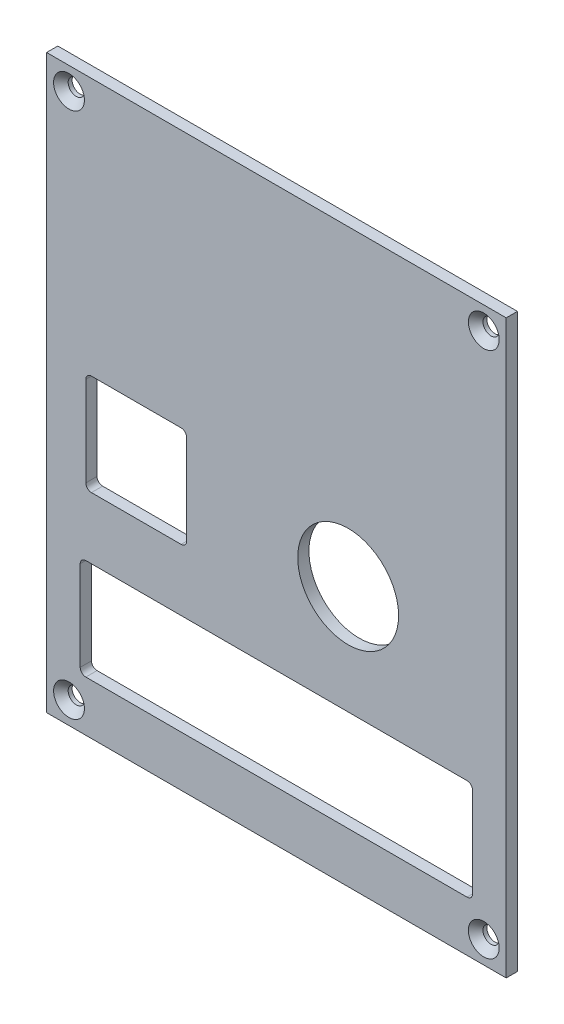
SolidWorks part; units mm, degrees
ref_plane "Front Plane" through (0, 0, 0) normal (0, 0, 1) x (1, 0, 0)
ref_plane "Top Plane" through (0, 0, 0) normal (0, 1, 0) x (1, 0, 0)
ref_plane "Right Plane" through (0, 0, 0) normal (1, 0, 0) x (0, 0, -1)
sketch "Sketch1" plane through (0, 0, 0) normal (0, 0, 1) x (1, 0, 0)
  line L1 (-49.4982, 55.7269) -> (32.5018, 55.7269)
  line L2 (-49.4982, 55.7269) -> (-49.4982, -46.2731)
  line L3 (-49.4982, -46.2731) -> (32.5018, -46.2731)
  line L4 (32.5018, 55.7269) -> (32.5018, -46.2731)
  dimension "D1" = 82
  dimension "D2" = 102
extrude "Boss-Extrude1" add sketch "Sketch1" along normal blind 2
sketch "Sketch2" plane through (0, 0, 2) normal (0, 0, 1) x (1, 0, 0)
  line L3 (-42.4982, -19.2731) -> (25.5018, -19.2731)
  line L4 (-43.4982, -20.2731) -> (-43.4982, -36.2731)
  line L5 (-42.4982, -37.2731) -> (25.5018, -37.2731)
  line L6 (26.5018, -20.2731) -> (26.5018, -36.2731)
  line L7 (-49.4982, 55.7269) -> (-49.4982, -46.2731) construction
  line L8 (-49.4982, -46.2731) -> (32.5018, -46.2731) construction
  line L15 (-41.4982, 9.7269) -> (-25.4982, 9.7269)
  line L16 (-42.4982, 8.7269) -> (-42.4982, -7.2731)
  line L17 (-41.4982, -8.2731) -> (-25.4982, -8.2731)
  line L18 (-24.4982, 8.7269) -> (-24.4982, -7.2731)
  arc A2 (25.5018, -19.2731) -> (26.5018, -20.2731) centre (25.5018, -20.2731) cw
  arc A3 (-43.4982, -36.2731) -> (-42.4982, -37.2731) centre (-42.4982, -36.2731) ccw
  arc A4 (25.5018, -37.2731) -> (26.5018, -36.2731) centre (25.5018, -36.2731) ccw
  arc A5 (-42.4982, -19.2731) -> (-43.4982, -20.2731) centre (-42.4982, -20.2731) ccw
  arc A6 (-42.4982, -7.2731) -> (-41.4982, -8.2731) centre (-41.4982, -7.2731) ccw
  arc A7 (-25.4982, -8.2731) -> (-24.4982, -7.2731) centre (-25.4982, -7.2731) ccw
  arc A8 (-25.4982, 9.7269) -> (-24.4982, 8.7269) centre (-25.4982, 8.7269) cw
  arc A9 (-41.4982, 9.7269) -> (-42.4982, 8.7269) centre (-41.4982, 8.7269) ccw
  circle A11 centre (4.3018, 0.1122) radius 9
  point P11 (26.5018, -19.2731)
  point P14 (-43.4982, -37.2731)
  point P18 (26.5018, -37.2731)
  point P27 (-24.4982, -8.2731)
  point P30 (-24.4982, 9.7269)
  point P33 (-42.4982, 9.7269)
  dimension "D1" = 70
  dimension "D5" = 1
  dimension "D6" = 1
  dimension "D11" = 1
  dimension "D12" = 18
  dimension "D2" = 6
  dimension "D3" = 18
  dimension "D4" = 9
  dimension "D7" = 18
  dimension "D8" = 18
  dimension "D9" = 7
  dimension "D10" = 11
extrude "Cut-Extrude2" cut sketch "Sketch2" against normal blind 2
sketch "Sketch16" plane through (0, 0, 2) normal (0, 0, 1) x (1, 0, 0)
  line L0 (-49.4982, 55.7269) -> (-49.4982, -46.2731) construction
  line L1 (-49.4982, -46.2731) -> (32.5018, -46.2731) construction
  line L2 (32.5018, 55.7269) -> (-49.4982, 55.7269) construction
  line L3 (32.5018, -46.2731) -> (32.5018, 55.7269) construction
  point P0 (-45.4982, -42.2731)
  point P1 (28.5018, -42.2731)
  point P2 (28.5018, 51.7269)
  point P3 (-45.4982, 51.7269)
  point P12 (0, 0)
  point P13 (0, 0)
  point P14 (-48.8946, 47.7821)
  dimension "D1" = 4
  dimension "D2" = 4
  dimension "D3" = 4
  dimension "D4" = 4
  dimension "D5" = 4
  dimension "D6" = 4
  dimension "D7" = 4
  dimension "D8" = 4
hole_wizard "CSK for M2.5 Countersunk Flat Head Screw2" positions "Sketch17" profile "Sketch18" countersink size "M2.5" standard "ISO" end condition through all
sketch "Sketch17" plane through (0, 0, 2) normal (0, 0, 1) x (1, 0, 0)
  point P0 (-45.4982, 51.7269)
  point P3 (-45.4982, -42.2731)
  point P6 (28.5018, -42.2731)
  point P9 (28.5018, 51.7269)
sketch "Sketch18" plane through (-45.4982, 51.7269, 2) normal (1, 0, 0) x (0, -1, 0)
  line L0 (0, 0) -> (0, 2)
  line L1 (0, 2) -> (1.45, 2)
  line L2 (1.45, 2) -> (1.45, 1.3)
  line L3 (1.45, 1.3) -> (2.75, 0)
  line L5 (2.75, 0) -> (0, 0)
  line L6 (-1.45, 1.3) -> (-2.75, 0) construction
  line L11 (0, -6.35) -> (0, 107.95) construction
  dimension "Thru Hole Dia." = 2.9
  dimension "Thru Hole Depth" = 2
  dimension "Near C'Sink Dia." = 5.5
  dimension "Near C'Sink Angle" = 90
